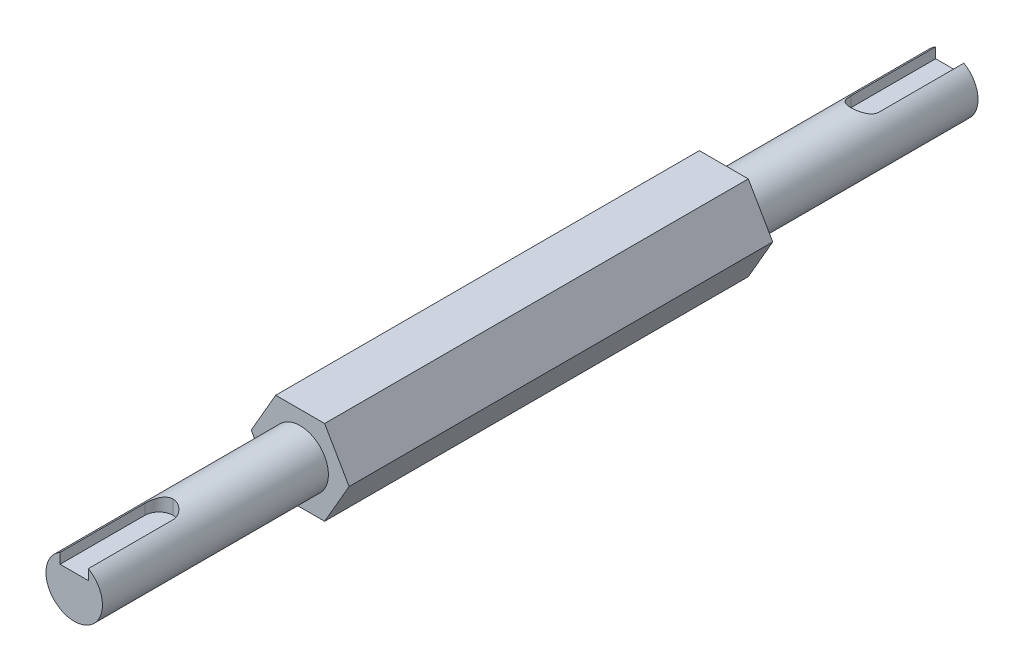
SolidWorks part; units mm, degrees
material "Plain Carbon Steel"
ref_plane "Front" through (0, 0, 0) normal (0, 0, 1) x (1, 0, 0)
ref_plane "Top" through (0, 0, 0) normal (0, 1, 0) x (1, 0, 0)
ref_plane "Right" through (0, 0, 0) normal (1, 0, 0) x (0, 0, -1)
sketch "Sketch1" plane through (0, 0, 0) normal (0, 0, 1) x (1, 0, 0)
  line L1 (8.6603, 15) -> (-8.6603, 15)
  line L2 (-8.6603, 15) -> (-17.3205, 0)
  line L3 (-17.3205, 0) -> (-8.6603, -15)
  line L4 (-8.6603, -15) -> (8.6603, -15)
  line L5 (8.6603, -15) -> (17.3205, 0)
  line L6 (17.3205, 0) -> (8.6603, 15)
  circle A0 centre (0, 0) radius 15 construction
  dimension "D1" = 30
extrude "Boss-Extrude1" add sketch "Sketch1" along normal mid plane 150
sketch "Sketch2" plane through (0, 0, 75) normal (0, 0, 1) x (1, 0, 0)
  circle A0 centre (0, 0) radius 10
  dimension "D1" = 20
extrude "Boss-Extrude2" add sketch "Sketch2" along normal blind 80
sketch "Sketch3" plane through (0, 0, -75) normal (0, 0, -1) x (-1, 0, 0)
  circle A0 centre (0, 0) radius 10
  circle A1 centre (0, 0) radius 10 construction
extrude "Boss-Extrude3" add sketch "Sketch3" along normal blind 80
sketch "Sketch4" plane through (0, 0, 155) normal (0, 0, 1) x (1, 0, 0)
  line L1 (-5, 23.6468) -> (5, 23.6468)
  line L2 (-5, 23.6468) -> (-5, 5)
  line L3 (-5, 5) -> (5, 5)
  line L4 (5, 23.6468) -> (5, 5)
  line L5 (-5, 23.6468) -> (5, 5) construction
  line L6 (-5, 5) -> (5, 23.6468) construction
  circle A0 centre (0, 0) radius 10 construction
  point P0 (0, 14.3234)
  point P5 (0, 0)
  dimension "D1" = 10
  dimension "D2" = 15
extrude "Cut-Extrude1" cut sketch "Sketch4" against normal blind 35
fillet "Fillet1" radius 5 2 edges at (5, 6.8301, 120) (-5, 6.8301, 120)
mirror "Mirror1" about plane through (0, 0, 0) normal (0, 0, 1) of "Fillet1", "Cut-Extrude1"
ref_axis "Axis1" through (0, 0, -80.9) along (0, 0, 1)
